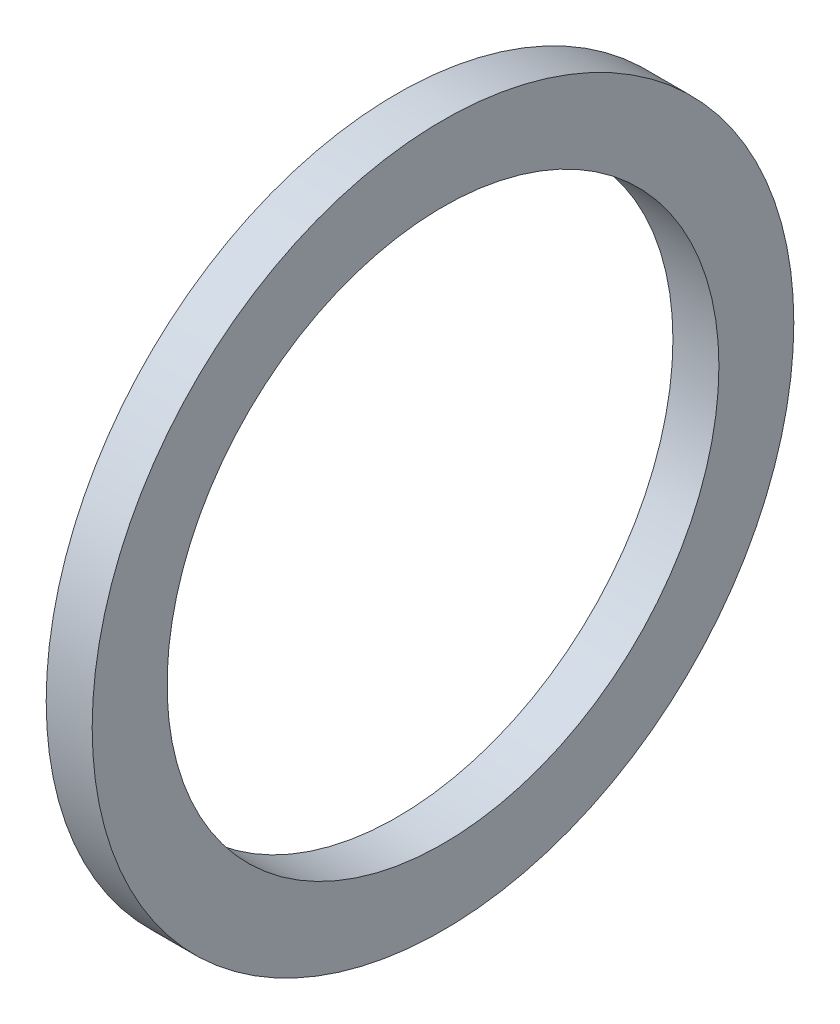
SolidWorks part; units mm, degrees
ref_plane "Front Plane" through (0, 0, 0) normal (0, 0, 1) x (1, 0, 0)
ref_plane "Top Plane" through (0, 0, 0) normal (0, 1, 0) x (1, 0, 0)
ref_plane "Right Plane" through (0, 0, 0) normal (1, 0, 0) x (0, 0, -1)
sketch "Sketch1" plane through (0, 0, 0) normal (1, 0, 0) x (0, 0, -1)
  circle A0 centre (0, 0) radius 76.29
  circle A1 centre (0, 0) radius 60
  dimension "D1" = 152.58
  dimension "D2" = 120
extrude "Boss-Extrude1" add sketch "Sketch1" along normal blind 10
sketch "Sketch2" plane through (10, 0, 0) normal (1, 0, 0) x (0, 0, -1)
  line L0 (87.8602, 0) -> (-82.133, 0) construction
  point P3 (-67, 0)
  point P4 (0, 0)
  point P5 (0, 0)
  point P6 (0, 0)
  point P7 (0, 0)
  point P8 (0, 0)
  dimension "D1" = 67
